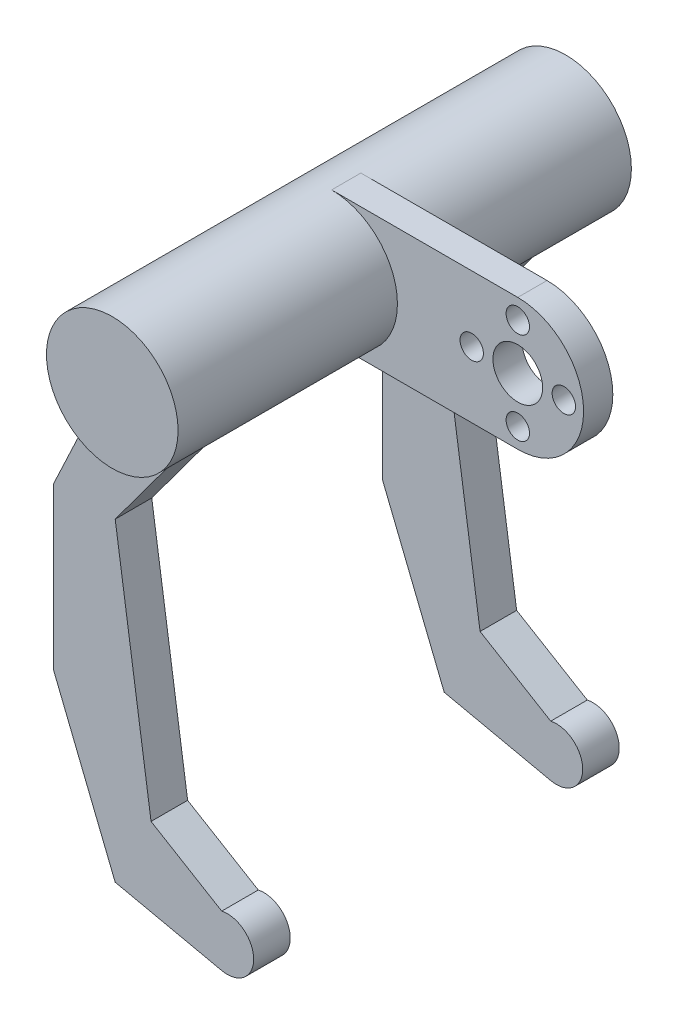
SolidWorks part; units mm, degrees
ref_plane "Front Plane" through (0, 0, 0) normal (0, 0, 1) x (1, 0, 0)
ref_plane "Top Plane" through (0, 0, 0) normal (0, 1, 0) x (1, 0, 0)
ref_plane "Right Plane" through (0, 0, 0) normal (1, 0, 0) x (0, 0, -1)
sketch "Sketch2" plane through (0, 0, 0) normal (0, 0, 1) x (1, 0, 0)
  circle A0 centre (0, 0) radius 11.43
  dimension "D1" = 22.86
extrude "Boss-Extrude1" add sketch "Sketch2" along normal blind 5.08
sketch "Sketch7" plane through (0, 0, 0) normal (0, 0, -1) x (-1, 0, 0)
  line L1 (0, 11.43) -> (32.3349, 11.43)
  line L2 (0, 11.43) -> (0, -11.43)
  line L3 (0, -11.43) -> (32.3349, -11.43)
  circle A1 centre (0, 0) radius 11.43 construction
  arc A2 (32.3349, 11.43) -> (32.3349, -11.43) centre (32.3349, 0) cw
extrude "Boss-Extrude2" add sketch "Sketch7" against normal blind 5.08
ref_plane "Plane1" through (0, 0, -31.75) normal (0, 0, 1) x (1, 0, 0)
sketch "Sketch4" plane through (0, 0, 0) normal (0, 0, -1) x (-1, 0, 0)
  circle A0 centre (0, 0) radius 4.318
  circle A1 centre (0, -8.001) radius 2.032
  dimension "D1" = 8.001
extrude "Cut-Extrude1" cut sketch "Sketch4" against normal blind 5.08
pattern_circular "CirPattern1" count 4 over 360 about axis through (0, 0, 5.08) along (0, 0, -1) of "Cut-Extrude1"
ref_plane "Plane2" through (-27.94, 0, 0) normal (1, 0, 0) x (0, 0, -1)
sketch "Sketch9" plane through (0, 0, 5.08) normal (0, 0, 1) x (1, 0, 0)
  circle A0 centre (-32.3349, 0) radius 11.43
extrude "Boss-Extrude3" add sketch "Sketch9" along normal blind 38.1 and the other way blind 40.64
sketch "Sketch10" plane through (0, 0, -31.75) normal (0, 0, 1) x (1, 0, 0)
  line L0 (-43.2583, -30.2196) -> (-20.9049, 0)
  line L1 (-39.7308, 0.0259) -> (-53.9503, -30.2196)
  line L2 (-53.9503, -58.3083) -> (-43.2583, -84.8421)
  line L3 (-43.2583, -84.8421) -> (-24.7566, -88.8741)
  line L4 (-24.7566, -79.9341) -> (-37.0287, -72.5822)
  line L5 (-37.0287, -72.5822) -> (-43.2583, -30.2196)
  line L6 (-53.9503, -30.2196) -> (-53.9503, -58.3083)
  line L7 (-20.9049, 0) -> (-39.7308, 0.0259)
  line L9 (-32.0617, 0.0259) -> (-32.3349, 0)
  arc A0 (-24.7566, -88.8741) -> (-24.7566, -79.9341) centre (-23.7825, -84.4041) ccw
  arc A1 (-32.3349, -11.43) -> (-32.3349, 11.43) centre (-32.3349, 0) ccw construction
extrude "Boss-Extrude4" add sketch "Sketch10" along normal blind 6.35 contours L3 A0 L4 L5 L0 L7 L1 L6 L2 region at (-41.0888, -51.5399, -31.75)
mirror "Mirror1" about plane through (0, 0, 0) normal (0, 0, 1) of "Boss-Extrude4"
